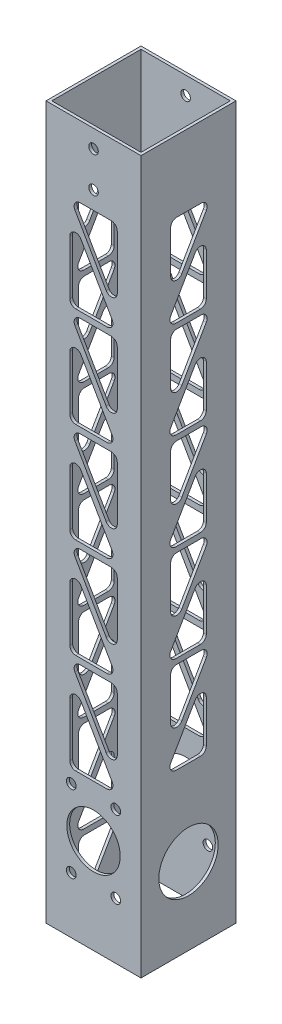
SolidWorks part; units mm, degrees
material "6061 Alloy"
ref_plane "Front Plane" through (0, 0, 0) normal (0, 0, 1) x (1, 0, 0)
ref_plane "Top Plane" through (0, 0, 0) normal (0, 1, 0) x (1, 0, 0)
ref_plane "Right Plane" through (0, 0, 0) normal (1, 0, 0) x (0, 0, -1)
sketch "Sketch1" plane through (0, 0, 0) normal (0, 1, 0) x (1, 0, 0)
  line L1 (25.4, 25.4) -> (-25.4, 25.4)
  line L2 (25.4, 25.4) -> (25.4, -25.4)
  line L3 (25.4, -25.4) -> (-25.4, -25.4)
  line L4 (-25.4, 25.4) -> (-25.4, -25.4)
  line L5 (25.4, 25.4) -> (-25.4, -25.4) construction
  line L6 (25.4, -25.4) -> (-25.4, 25.4) construction
  point P0 (0, 0)
  dimension "D1" = 50.8
extrude "Extrude-Thin1" add sketch "Sketch1" along normal blind 381 thin thin type one direction reverse wall 1.524
sketch "Sketch2" plane through (0, 0, 0) normal (0, 0, 1) x (1, 0, 0)
  line L0 (-36.2563, 68.2625) -> (38.5702, 68.2625) construction
  line L1 (-25.4, 0) -> (25.4, 0) construction
  line L2 (-25.4, 50.8) -> (25.4, 50.8) construction
  line L6 (25.4, 381) -> (25.4, 0) construction
  line L7 (-25.4, 381) -> (-25.4, 0) construction
  line L8 (-11.9062, 30.1778) -> (11.9063, 30.1778) construction
  line L9 (-11.9062, 71.4222) -> (11.9063, 71.4222) construction
  circle A0 centre (0, 50.8) radius 14.3002
  circle A1 centre (0, 50.8) radius 23.8125 construction
  circle A2 centre (-11.9062, 30.1778) radius 2.5908
  circle A3 centre (11.9063, 30.1778) radius 2.5908
  circle A4 centre (11.9063, 71.4222) radius 2.5908
  circle A5 centre (-11.9062, 71.4222) radius 2.5908
  point P11 (0, 50.8)
  dimension "D1" = 28.6004
  dimension "D3" = 17.4625
  dimension "D4" = 47.625
  dimension "D6" = 5.1816
  dimension "D2" = 50.8
  dimension "D5" = 60
extrude "Cut-Extrude1" cut sketch "Sketch2" along normal through all both and the other way through all
sketch "Sketch3" plane through (25.4, 0, 0) normal (1, 0, 0) x (0, 0, -1)
  line L0 (-25.4, 50.8) -> (25.4, 50.8) construction
  line L1 (-25.4, 65.1002) -> (-25.4, 36.4998) construction
  line L3 (25.4, 381) -> (25.4, 0) construction
  circle A0 centre (0, 41.275) radius 15.875
  point P9 (0, 50.8)
  dimension "D1" = 31.75
  dimension "D2" = 9.525
extrude "Cut-Extrude2" cut sketch "Sketch3" against normal up to surface (1.524 mm away) up to face at (23.876, 190.5, 0)
sketch "Sketch4" plane through (0, 0, 25.4) normal (0, 0, 1) x (1, 0, 0)
  line L0 (-25.4, 381) -> (25.4, 381) construction
  circle A0 centre (0, 371.475) radius 2.54
  circle A1 centre (0, 352.425) radius 2.54
  dimension "D1" = 5.08
  dimension "D2" = 9.525
  dimension "D3" = 28.575
hole_wizard "#10 Clearance Hole1" positions "Sketch5" profile "Sketch6" hole size "#10" standard "ANSI Inch" end condition through all
sketch "Sketch5" plane through (0, 0, 25.4) normal (0, 0, 1) x (1, 0, 0)
  point P0 (0, 352.425)
  point P3 (0, 371.475)
sketch "Sketch6" plane through (0, 352.425, 25.4) normal (1, 0, 0) x (0, -1, 0)
  line L0 (0, 0) -> (0, 50.8)
  line L1 (0, 50.8) -> (2.5527, 50.8)
  line L2 (2.5527, 50.8) -> (2.5527, 0)
  line L5 (2.5527, 0) -> (0, 0)
  line L11 (0, -6.35) -> (0, 107.95) construction
  dimension "Thru Hole Dia." = 5.1054
  dimension "Thru Hole Depth" = 50.8
sketch "Sketch7" plane through (0, 0, 25.4) normal (0, 0, 1) x (1, 0, 0)
  line L0 (-12.7, 381) -> (-12.7, 0) construction
  line L1 (12.7, 381) -> (12.7, 0) construction
  line L2 (-12.7, 0) -> (-25.4, 0) construction
  line L3 (-25.4, 0) -> (25.4, 0) construction
  line L4 (-25.4, 381) -> (-25.4, 0) construction
  line L5 (12.7, 0) -> (25.4, 0) construction
  line L6 (-25.4, 381) -> (25.4, 381) construction
  line L7 (-12.7, 342.9) -> (12.7, 342.9) construction
  line L8 (-12.7, 79.375) -> (12.7, 79.375) construction
  line L9 (-7.2007, 342.9) -> (9.525, 342.9)
  line L10 (12.7, 339.725) -> (12.7, 310.7552)
  line L11 (6.7754, 309.1677) -> (-9.9504, 338.1375)
  line L12 (-9.525, 292.5559) -> (7.2007, 292.5559)
  line L13 (-12.7, 295.7309) -> (-12.7, 324.7007)
  line L14 (-6.7754, 326.2882) -> (9.9504, 297.3184)
  line L15 (-0.1024, 314.7303) -> (2.6473, 316.3178) construction
  line L16 (-7.2007, 289.3809) -> (9.525, 289.3809)
  line L17 (12.7, 286.2059) -> (12.7, 257.2361)
  line L18 (6.7754, 255.6486) -> (-9.9504, 284.6184)
  line L19 (-12.7, 242.2118) -> (-12.7, 271.1816)
  line L20 (-9.525, 239.0368) -> (7.2007, 239.0368)
  line L21 (-6.7754, 272.7691) -> (9.9504, 243.7993)
  line L34 (-7.2007, 342.9) -> (-7.2007, 289.3809) construction
  line L35 (-7.2007, 235.8618) -> (9.525, 235.8618)
  line L36 (12.7, 232.6868) -> (12.7, 203.717)
  line L37 (6.7754, 202.1295) -> (-9.9504, 231.0993)
  line L38 (-12.7, 188.6927) -> (-12.7, 217.6626)
  line L39 (-9.525, 185.5177) -> (7.2007, 185.5177)
  line L40 (-6.7754, 219.2501) -> (9.9504, 190.2802)
  line L41 (-7.2007, 182.3427) -> (9.525, 182.3427)
  line L42 (12.7, 179.1677) -> (12.7, 150.1979)
  line L43 (6.7754, 148.6104) -> (-9.9504, 177.5802)
  line L44 (-12.7, 135.1736) -> (-12.7, 164.1435)
  line L45 (-9.525, 131.9986) -> (7.2007, 131.9986)
  line L46 (-6.7754, 165.731) -> (9.9504, 136.7611)
  line L47 (-7.2007, 128.8236) -> (9.525, 128.8236)
  line L48 (12.7, 125.6486) -> (12.7, 96.6788)
  line L49 (6.7754, 95.0913) -> (-9.9504, 124.0611)
  line L50 (-12.7, 81.6545) -> (-12.7, 110.6244)
  line L51 (-9.525, 78.4795) -> (7.2007, 78.4795)
  line L52 (-6.7754, 112.2119) -> (9.9504, 83.242)
  arc A0 (-9.9504, 338.1375) -> (-7.2007, 342.9) centre (-7.2007, 339.725) cw
  arc A1 (9.525, 342.9) -> (12.7, 339.725) centre (9.525, 339.725) cw
  arc A2 (12.7, 310.7552) -> (6.7754, 309.1677) centre (9.525, 310.7552) cw
  arc A3 (9.9504, 297.3184) -> (7.2007, 292.5559) centre (7.2007, 295.7309) cw
  arc A4 (-12.7, 324.7007) -> (-6.7754, 326.2882) centre (-9.525, 324.7007) cw
  arc A5 (-12.7, 295.7309) -> (-9.525, 292.5559) centre (-9.525, 295.7309) ccw
  arc A6 (12.7, 257.2361) -> (6.7754, 255.6486) centre (9.525, 257.2361) cw
  arc A7 (-9.9504, 284.6184) -> (-7.2007, 289.3809) centre (-7.2007, 286.2059) cw
  arc A8 (9.525, 289.3809) -> (12.7, 286.2059) centre (9.525, 286.2059) cw
  arc A9 (-12.7, 271.1816) -> (-6.7754, 272.7691) centre (-9.525, 271.1816) cw
  arc A10 (-12.7, 242.2118) -> (-9.525, 239.0368) centre (-9.525, 242.2118) ccw
  arc A11 (9.9504, 243.7993) -> (7.2007, 239.0368) centre (7.2007, 242.2118) cw
  arc A12 (12.7, 203.717) -> (6.7754, 202.1295) centre (9.525, 203.717) cw
  arc A13 (-9.9504, 231.0993) -> (-7.2007, 235.8618) centre (-7.2007, 232.6868) cw
  arc A14 (9.525, 235.8618) -> (12.7, 232.6868) centre (9.525, 232.6868) cw
  arc A15 (-12.7, 217.6626) -> (-6.7754, 219.2501) centre (-9.525, 217.6626) cw
  arc A16 (-12.7, 188.6927) -> (-9.525, 185.5177) centre (-9.525, 188.6927) ccw
  arc A17 (9.9504, 190.2802) -> (7.2007, 185.5177) centre (7.2007, 188.6927) cw
  arc A18 (12.7, 150.1979) -> (6.7754, 148.6104) centre (9.525, 150.1979) cw
  arc A19 (-9.9504, 177.5802) -> (-7.2007, 182.3427) centre (-7.2007, 179.1677) cw
  arc A20 (9.525, 182.3427) -> (12.7, 179.1677) centre (9.525, 179.1677) cw
  arc A21 (-12.7, 164.1435) -> (-6.7754, 165.731) centre (-9.525, 164.1435) cw
  arc A22 (-12.7, 135.1736) -> (-9.525, 131.9986) centre (-9.525, 135.1736) ccw
  arc A23 (9.9504, 136.7611) -> (7.2007, 131.9986) centre (7.2007, 135.1736) cw
  arc A24 (12.7, 96.6788) -> (6.7754, 95.0913) centre (9.525, 96.6788) cw
  arc A25 (-9.9504, 124.0611) -> (-7.2007, 128.8236) centre (-7.2007, 125.6486) cw
  arc A26 (9.525, 128.8236) -> (12.7, 125.6486) centre (9.525, 125.6486) cw
  arc A27 (-12.7, 110.6244) -> (-6.7754, 112.2119) centre (-9.525, 110.6244) cw
  arc A28 (-12.7, 81.6545) -> (-9.525, 78.4795) centre (-9.525, 81.6545) ccw
  arc A29 (9.9504, 83.242) -> (7.2007, 78.4795) centre (7.2007, 81.6545) cw
  point P31 (12.7, 298.9059)
  point P34 (12.7, 292.5559)
  point P37 (-12.7, 336.55)
  point P40 (-12.7, 292.5559)
  point P42 (0, 0)
  dimension "D5" = 3.175
  dimension "D1" = 12.7
  dimension "D2" = 38.1
  dimension "D3" = 79.375
  dimension "D4" = 30
  dimension "D7" = 3.175
  dimension "D8" = 3.175
  dimension "D6" = 5
extrude "Cut-Extrude3" cut sketch "Sketch7" against normal through all
sketch "Sketch8" plane through (-25.4, 0, 0) normal (-1, 0, 0) x (0, 0, 1)
  line L0 (-12.2746, 342.9) -> (9.525, 342.9) construction
  line L1 (-6.7754, 342.9) -> (6.35, 342.9)
  line L2 (9.525, 339.725) -> (9.525, 316.9912)
  line L3 (3.6004, 315.4037) -> (-9.525, 338.1375)
  line L4 (-6.35, 294.0294) -> (6.7754, 294.0294)
  line L5 (-9.525, 297.2044) -> (-9.525, 319.9382)
  line L6 (-3.6004, 321.5257) -> (9.525, 298.7919)
  line L7 (4.3689, 307.7225) -> (7.1185, 309.31) construction
  line L8 (-9.525, 381) -> (-9.525, 0) construction
  line L9 (-25.4, 0) -> (25.4, 0) construction
  line L10 (9.525, 0) -> (9.525, 381) construction
  line L11 (-25.4, 381) -> (25.4, 381) construction
  line L12 (-9.525, 392.3126) -> (-25.4, 392.3126) construction
  line L13 (-25.4, 381) -> (-25.4, 0) construction
  line L14 (9.525, 392.3126) -> (25.4, 392.3126) construction
  line L15 (25.4, 381) -> (25.4, 0) construction
  line L16 (-6.35, 242.2379) -> (6.7754, 242.2379)
  line L17 (-9.525, 245.4129) -> (-9.525, 268.1467)
  line L18 (-3.6004, 269.7342) -> (9.525, 247.0004)
  line L19 (9.525, 287.9334) -> (9.525, 265.1996)
  line L20 (3.6004, 263.6121) -> (-9.525, 286.3459)
  line L21 (-6.7754, 291.1084) -> (6.35, 291.1084)
  line L22 (-6.35, 190.4463) -> (6.7754, 190.4463)
  line L23 (-9.525, 193.6213) -> (-9.525, 216.3551)
  line L24 (-3.6004, 217.9426) -> (9.525, 195.2088)
  line L25 (9.525, 236.1419) -> (9.525, 213.4081)
  line L26 (3.6004, 211.8206) -> (-9.525, 234.5544)
  line L27 (-6.7754, 239.3169) -> (6.35, 239.3169)
  line L28 (-6.35, 138.6547) -> (6.7754, 138.6547)
  line L29 (-9.525, 141.8297) -> (-9.525, 164.5635)
  line L30 (-3.6004, 166.151) -> (9.525, 143.4172)
  line L31 (9.525, 184.3503) -> (9.525, 161.6165)
  line L32 (3.6004, 160.029) -> (-9.525, 182.7628)
  line L33 (-6.7754, 187.5253) -> (6.35, 187.5253)
  line L34 (-25.4, 87.3125) -> (25.4, 87.3125) construction
  line L35 (-6.35, 86.8632) -> (6.7754, 86.8632)
  line L36 (-9.525, 90.0382) -> (-9.525, 112.772)
  line L37 (-3.6004, 114.3595) -> (9.525, 91.6257)
  line L38 (9.525, 132.5587) -> (9.525, 109.8249)
  line L39 (3.6004, 108.2374) -> (-9.525, 130.9712)
  line L40 (-6.7754, 135.7337) -> (6.35, 135.7337)
  line L41 (-6.35, 35.0716) -> (6.7754, 35.0716)
  line L42 (-9.525, 38.2466) -> (-9.525, 60.9804)
  line L43 (-3.6004, 62.5679) -> (9.525, 39.8341)
  line L44 (9.525, 80.7672) -> (9.525, 58.0334)
  line L45 (3.6004, 56.4459) -> (-9.525, 79.1797)
  line L46 (-6.7754, 83.9422) -> (6.35, 83.9422)
  line L50 (9.525, 28.9756) -> (9.525, 6.2418)
  line L51 (3.6004, 4.6543) -> (-9.525, 27.3881)
  line L52 (-6.7754, 32.1506) -> (6.35, 32.1506)
  line L53 (-6.35, -16.7199) -> (6.7754, -16.7199) [skipped]
  line L54 (-3.6004, 10.7764) -> (9.525, -11.9574) [skipped]
  line L55 (-9.525, -13.5449) -> (-9.525, 9.1889) [skipped]
  arc A0 (-9.525, 338.1375) -> (-6.7754, 342.9) centre (-6.7754, 339.725) cw
  arc A1 (6.35, 342.9) -> (9.525, 339.725) centre (6.35, 339.725) cw
  arc A2 (9.525, 316.9912) -> (3.6004, 315.4037) centre (6.35, 316.9912) cw
  arc A3 (9.525, 298.7919) -> (6.7754, 294.0294) centre (6.7754, 297.2044) cw
  arc A4 (-9.525, 319.9382) -> (-3.6004, 321.5257) centre (-6.35, 319.9382) cw
  arc A5 (-9.525, 297.2044) -> (-6.35, 294.0294) centre (-6.35, 297.2044) ccw
  arc A6 (-9.525, 245.4129) -> (-6.35, 242.2379) centre (-6.35, 245.4129) ccw
  arc A7 (-9.525, 268.1467) -> (-3.6004, 269.7342) centre (-6.35, 268.1467) cw
  arc A8 (9.525, 247.0004) -> (6.7754, 242.2379) centre (6.7754, 245.4129) cw
  arc A9 (9.525, 265.1996) -> (3.6004, 263.6121) centre (6.35, 265.1996) cw
  arc A10 (6.35, 291.1084) -> (9.525, 287.9334) centre (6.35, 287.9334) cw
  arc A11 (-9.525, 286.3459) -> (-6.7754, 291.1084) centre (-6.7754, 287.9334) cw
  arc A12 (-9.525, 193.6213) -> (-6.35, 190.4463) centre (-6.35, 193.6213) ccw
  arc A13 (-9.525, 216.3551) -> (-3.6004, 217.9426) centre (-6.35, 216.3551) cw
  arc A14 (9.525, 195.2088) -> (6.7754, 190.4463) centre (6.7754, 193.6213) cw
  arc A15 (9.525, 213.4081) -> (3.6004, 211.8206) centre (6.35, 213.4081) cw
  arc A16 (6.35, 239.3169) -> (9.525, 236.1419) centre (6.35, 236.1419) cw
  arc A17 (-9.525, 234.5544) -> (-6.7754, 239.3169) centre (-6.7754, 236.1419) cw
  arc A18 (-9.525, 141.8297) -> (-6.35, 138.6547) centre (-6.35, 141.8297) ccw
  arc A19 (-9.525, 164.5635) -> (-3.6004, 166.151) centre (-6.35, 164.5635) cw
  arc A20 (9.525, 143.4172) -> (6.7754, 138.6547) centre (6.7754, 141.8297) cw
  arc A21 (9.525, 161.6165) -> (3.6004, 160.029) centre (6.35, 161.6165) cw
  arc A22 (6.35, 187.5253) -> (9.525, 184.3503) centre (6.35, 184.3503) cw
  arc A23 (-9.525, 182.7628) -> (-6.7754, 187.5253) centre (-6.7754, 184.3503) cw
  arc A24 (-9.525, 90.0382) -> (-6.35, 86.8632) centre (-6.35, 90.0382) ccw
  arc A25 (-9.525, 112.772) -> (-3.6004, 114.3595) centre (-6.35, 112.772) cw
  arc A26 (9.525, 91.6257) -> (6.7754, 86.8632) centre (6.7754, 90.0382) cw
  arc A27 (9.525, 109.8249) -> (3.6004, 108.2374) centre (6.35, 109.8249) cw
  arc A28 (6.35, 135.7337) -> (9.525, 132.5587) centre (6.35, 132.5587) cw
  arc A29 (-9.525, 130.9712) -> (-6.7754, 135.7337) centre (-6.7754, 132.5587) cw
  arc A30 (-9.525, 38.2466) -> (-6.35, 35.0716) centre (-6.35, 38.2466) ccw
  arc A31 (-9.525, 60.9804) -> (-3.6004, 62.5679) centre (-6.35, 60.9804) cw
  arc A32 (9.525, 39.8341) -> (6.7754, 35.0716) centre (6.7754, 38.2466) cw
  arc A33 (9.525, 58.0334) -> (3.6004, 56.4459) centre (6.35, 58.0334) cw
  arc A34 (6.35, 83.9422) -> (9.525, 80.7672) centre (6.35, 80.7672) cw
  arc A35 (-9.525, 79.1797) -> (-6.7754, 83.9422) centre (-6.7754, 80.7672) cw
  arc A39 (9.525, 6.2418) -> (3.6004, 4.6543) centre (6.35, 6.2418) cw
  arc A40 (6.35, 32.1506) -> (9.525, 28.9756) centre (6.35, 28.9756) cw
  arc A41 (-9.525, 27.3881) -> (-6.7754, 32.1506) centre (-6.7754, 28.9756) cw
  arc A42 (9.525, -11.9574) -> (6.7754, -16.7199) centre (6.7754, -13.5449) cw [skipped]
  arc A43 (-9.525, 9.1889) -> (-3.6004, 10.7764) centre (-6.35, 9.1889) cw [skipped]
  arc A44 (-9.525, -13.5449) -> (-6.35, -16.7199) centre (-6.35, -13.5449) ccw [skipped]
  point P148 (6.7754, 6.0971)
  point P150 (7.1718, 3.175)
  dimension "D2" = 3.175
  dimension "D1" = 30
  dimension "D3" = 38.1
  dimension "D4" = 15.875
  dimension "D5" = 3.175
  dimension "D7" = 3.175
  dimension "D8" = 87.3125
  dimension "D6" = 7
extrude "Cut-Extrude4" cut sketch "Sketch8" against normal through all contours A14 L24 A13 L23 A12 L22 | A17 L26 A15 L25 A16 L27 | A8 L18 A7 L17 A6 L16 | A11 L20 A9 L19 A10 L21 | L5 A5 L4 A3 L6 A4 | A2 L2 A1 L1 A0 L3 | A23 L32 A21 L31 A22 L33 | A20 L30 A19 L29 A18 L28 | A29 L39 A27 L38 A28 L40 | A26 L37 A25 L36 A24 L35 region at (-25.4, 331.265, 2.0868) region at (-25.4, 305.6645, -2.0868) region at (-25.4, 253.8729, -2.0868) region at (-25.4, 279.4734, 2.0868) region at (-25.4, 202.0813, -2.0868) region at (-25.4, 227.6819, 2.0868) region at (-25.4, 150.2898, -2.0868) region at (-25.4, 175.8903, 2.0868) region at (-25.4, 98.4982, -2.0868) region at (-25.4, 124.0987, 2.0868)
extrude "Cut-Extrude5" cut sketch "Sketch8<4>" against normal up to next contours A41 L51 A39 L50 A40 L52 | A32 L43 A31 L42 A30 L41 | A35 L45 A33 L44 A34 L46 region at (-25.4, 46.7066, -2.0868) region at (-25.4, 72.3072, 2.0868) region at (-25.4, 20.5156, 2.0868)
sketch "Sketch8<4>" plane through (-25.4, 0, 0) normal (-1, 0, 0) x (0, 0, 1) same geometry as "Sketch8"
